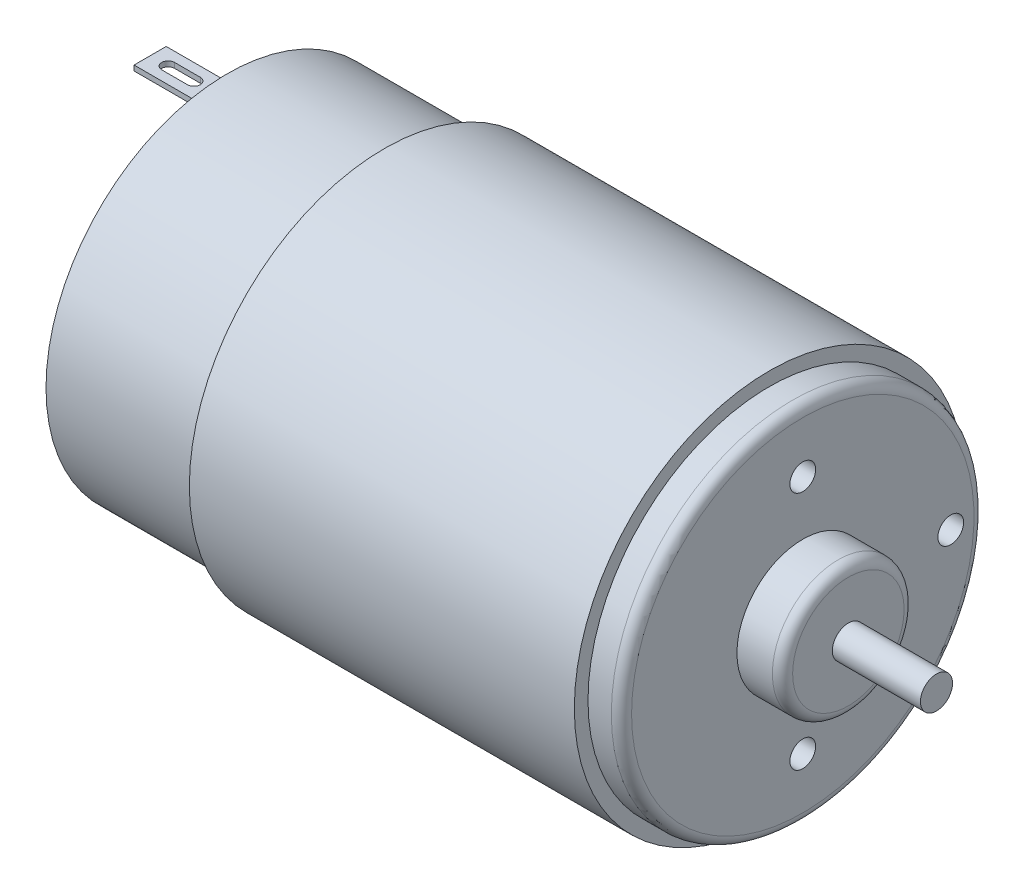
SolidWorks part; units mm, degrees
ref_plane "Front" through (0, 0, 0) normal (0, 0, 1) x (1, 0, 0)
ref_plane "Top" through (0, 0, 0) normal (0, 1, 0) x (1, 0, 0)
ref_plane "Right" through (0, 0, 0) normal (1, 0, 0) x (0, 0, -1)
sketch "Sketch1" plane through (0, 0, 0) normal (0, 0, 1) x (1, 0, 0)
  line L0 (0, 0) -> (98.9182, 0) construction
  line L1 (0, 0) -> (75, 0)
  line L2 (2, 5.1) -> (2, 1.585)
  line L3 (2, 1.585) -> (0, 1.585)
  line L9 (75, 0) -> (75, 1.585)
  line L10 (75, 1.585) -> (66.3, 1.585)
  line L11 (66.3, 1.585) -> (66.3, 6.5)
  line L12 (66.3, 6.5) -> (61.8, 6.5)
  line L17 (61.8, 6.5) -> (61.8, 17.9)
  line L18 (61.8, 17.9) -> (58.5, 17.9)
  line L19 (58.5, 17.9) -> (58.5, 19.25)
  line L20 (58.5, 19.25) -> (20.5, 19.25)
  line L21 (20.5, 19.25) -> (20.5, 17.9)
  line L22 (20.5, 17.9) -> (5, 17.9)
  line L23 (5, 17.9) -> (5, 5.1)
  line L28 (5, 5.1) -> (2, 5.1)
  line L29 (0, 1.585) -> (0, 0)
  dimension "D1" = 13
  dimension "D2" = 3.17
  dimension "D3" = 75
  dimension "D4" = 13.2
  dimension "D5" = 4.5
  dimension "D6" = 3.3
  dimension "D7" = 38
  dimension "D8" = 2
  dimension "D9" = 3
  dimension "D10" = 35.8
  dimension "D11" = 38.5
  dimension "D12" = 10.2
revolve "Revolve1" add sketch "Sketch1" angle 360 about L0
sketch "Sketch2" plane through (61.8, 0, 0) normal (1, 0, 0) x (0, 0, -1)
  line L0 (0, 0) -> (0, 18.9264) construction
  circle A0 centre (0, 11.84) radius 1.27
  dimension "D2" = 2.54
  dimension "D1" = 11.84
extrude "Extrude1" cut sketch "Sketch2" against normal blind 5.08
ref_axis "Axis1" through (20.5, 0, 0) along (-1, 0, 0)
pattern_circular "CirPattern1" count 2 over 360 about axis through (20.5, 0, 0) along (-1, 0, 0) of "Extrude1"
sketch "Sketch6" plane through (61.8, 0, 0) normal (1, 0, 0) x (0, 0, -1)
  circle A0 centre (14.605, 0) radius 1.27
  circle A1 centre (0, 11.84) radius 1.27 construction
  dimension "D1" = 14.605
extrude "Extrude5" cut sketch "Sketch6" against normal up to surface (5.08 mm away) up to face at (56.72, 11.84, -1.27)
sketch "Sketch3" plane through (58.5, 0, 0) normal (1, 0, 0) x (0, 0, -1)
  line L0 (17.8633, 1.145) -> (19.8633, 1.145)
  line L1 (0, 0) -> (21.5701, 0) construction
  line L2 (17.8633, -1.145) -> (19.8633, -1.145)
  line L3 (19.8633, -1.145) -> (19.8633, 1.145)
  circle A0 centre (0, 0) radius 17.9 construction
  arc A1 (17.8633, -1.145) -> (17.8633, 1.145) centre (0, 0) ccw
  dimension "D1" = 2
  dimension "D2" = 2.29
extrude "Extrude2" cut sketch "Sketch3" against normal up to next
ref_plane "Plane1" through (0, 15.62, 0) normal (0, 1, 0) x (-1, 0, 0)
sketch "Sketch4" plane through (0, 15.62, 0) normal (0, 1, 0) x (-1, 0, 0)
  line L0 (2.62, 1.5875) -> (-5, 1.5875)
  line L1 (-5, 1.5875) -> (-5, -1.5875)
  line L2 (-5, -1.5875) -> (2.62, -1.5875)
  line L3 (2.62, -1.5875) -> (2.62, 1.5875)
  line L4 (0, 0) -> (8.7606, 0) construction
  line L5 (-5, -17.9) -> (-5, 17.9) construction
  dimension "D1" = 3.175
  dimension "D2" = 7.62
extrude "Extrude3" add sketch "Sketch4" against normal blind 0.51
sketch "Sketch5" plane through (0, 15.62, 0) normal (0, 1, 0) x (1, 0, 0)
  line L0 (-0.84, 0.635) -> (1.7, 0.635)
  line L1 (1.7, -0.635) -> (-0.84, -0.635)
  line L2 (-2.62, 0) -> (2.149, 0) construction
  line L3 (-2.62, 1.5875) -> (-2.62, -1.5875) construction
  line L4 (-0.84, -0.9144) -> (-0.84, 0.6951) construction
  line L5 (1.7, -0.864) -> (1.7, 0.7709) construction
  arc A0 (1.7, -0.635) -> (1.7, 0.635) centre (1.7, 0) ccw
  arc A1 (-0.84, 0.635) -> (-0.84, -0.635) centre (-0.84, 0) ccw
  dimension "D1" = 0.635
  dimension "D2" = 2.54
  dimension "D4" = 1.78
extrude "Extrude4" cut sketch "Sketch5" against normal up to next
mirror "Mirror1" about plane through (0, 0, 0) normal (0, 1, 0) of "Extrude4", "Extrude3"
fillet "Filete1" radius 1 3 edges at (66.3, 0, 6.5) (61.8, 0, 17.9) (2, 0, 5.1)
